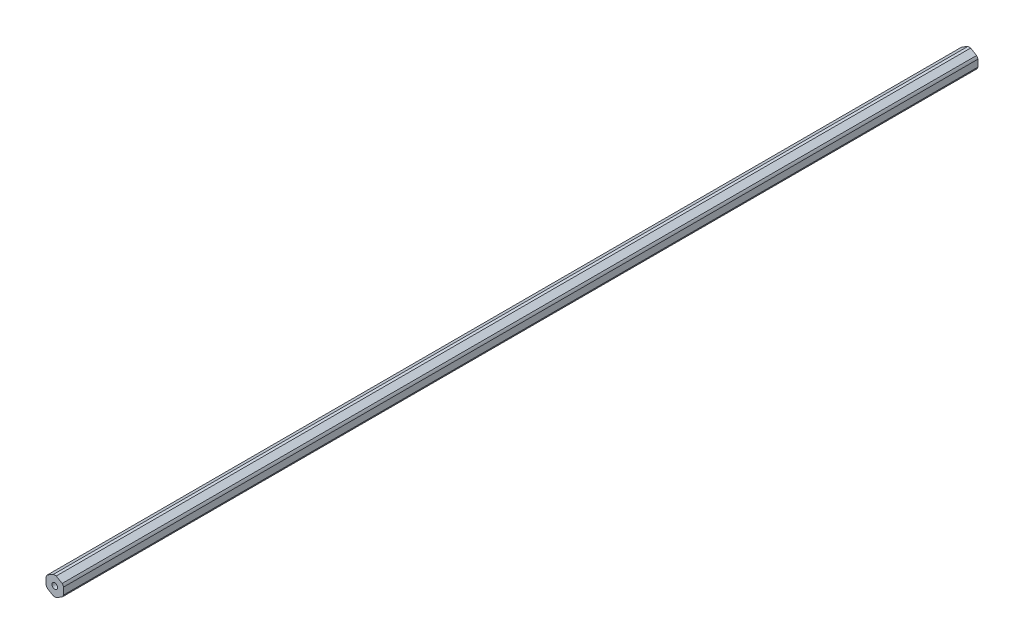
SolidWorks part; units mm, degrees
material "7075-T6 (SN)"
ref_plane "Front Plane" through (0, 0, 0) normal (0, 0, 1) x (1, 0, 0)
ref_plane "Top Plane" through (0, 0, 0) normal (0, 1, 0) x (1, 0, 0)
ref_plane "Right Plane" through (0, 0, 0) normal (1, 0, 0) x (0, 0, -1)
sketch "Sketch1" plane through (0, 0, 0) normal (0, 0, 1) x (1, 0, 0)
  line L1 (6.35, 3.6662) -> (0, 7.3323)
  line L2 (0, 7.3323) -> (-6.35, 3.6662)
  line L3 (-6.35, 3.6662) -> (-6.35, -3.6662)
  line L4 (-6.35, -3.6662) -> (0, -7.3323)
  line L5 (0, -7.3323) -> (6.35, -3.6662)
  line L6 (6.35, -3.6662) -> (6.35, 3.6662)
  circle A0 centre (0, 0) radius 6.35 construction
  circle A1 centre (0, 0) radius 6.8199
  dimension "D1" = 12.7
  dimension "D2" = 13.6398
extrude "Boss-Extrude1" add sketch "Sketch1" along normal blind 660.4 contours L6 A1 L1 L2 L3 L4 L5 region at (0, 0, 0)
hole_wizard "#10-32 Tapped Hole1" positions "Sketch2" profile "Sketch3" tap size "#10-32" standard "ANSI Inch"
sketch "Sketch2" plane through (0, 0, 660.4) normal (0, 0, 1) x (1, 0, 0)
  point P0 (0, 0)
sketch "Sketch3" plane through (0, 0, 660.4) normal (1, 0, 0) x (0, -1, 0)
  line L0 (0, 0) -> (0, 13.2428)
  line L1 (0, 13.2428) -> (2.0193, 12.0294)
  line L2 (2.0193, 12.0294) -> (2.0193, 0)
  line L5 (2.0193, 0) -> (0, 0)
  line L10 (0, 13.2428) -> (-2.0193, 12.0294) construction
  line L11 (0, -6.35) -> (0, 107.95) construction
  dimension "Tap Drill Dia." = 4.0386
  dimension "Tap Drill Depth" = 12.0294
  dimension "Drill Angle" = 118
cosmetic thread "Hole Thread1" parameters "D1"=9.652, "D2"=4.826
hole_wizard "#10-32 Tapped Hole2" positions "Sketch4" profile "Sketch5" tap size "#10-32" standard "ANSI Inch"
sketch "Sketch4" plane through (0, 0, 0) normal (0, 0, -1) x (-1, 0, 0)
  point P0 (0, 0)
sketch "Sketch5" plane through (0, 0, 0) normal (1, 0, 0) x (0, 1, 0)
  line L0 (0, 0) -> (0, 13.2428)
  line L1 (0, 13.2428) -> (2.0193, 12.0294)
  line L2 (2.0193, 12.0294) -> (2.0193, 0)
  line L5 (2.0193, 0) -> (0, 0)
  line L10 (0, 13.2428) -> (-2.0193, 12.0294) construction
  line L11 (0, -6.35) -> (0, 107.95) construction
  dimension "Tap Drill Dia." = 4.0386
  dimension "Tap Drill Depth" = 12.0294
  dimension "Drill Angle" = 118
cosmetic thread "Hole Thread2" parameters "D1"=9.652, "D2"=4.826
